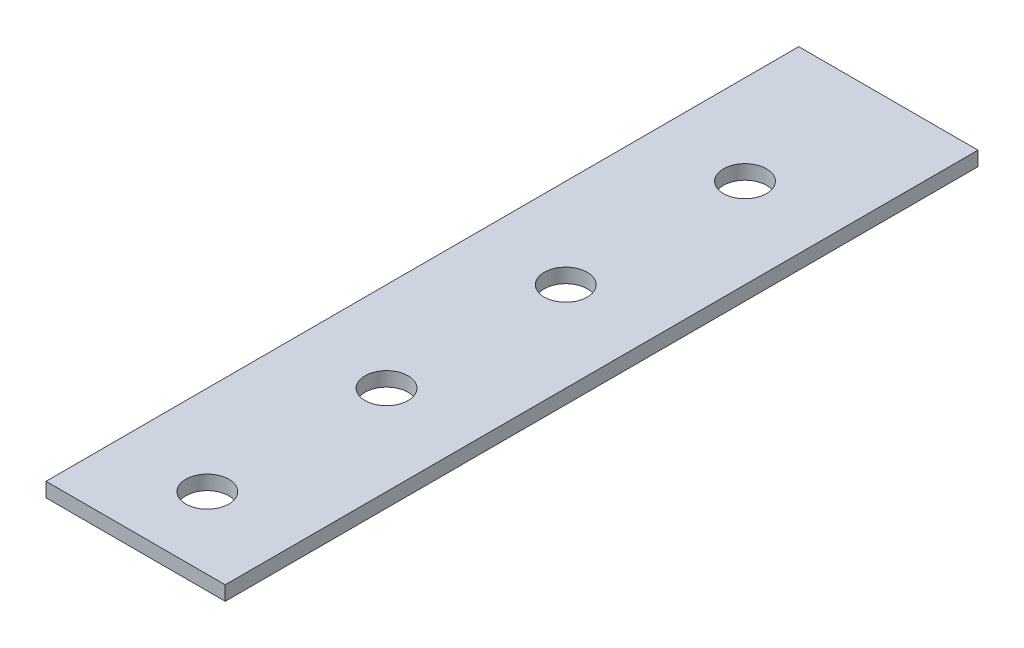
SolidWorks part; units mm, degrees
ref_plane "Front Plane" through (0, 0, 0) normal (0, 0, 1) x (1, 0, 0)
ref_plane "Top Plane" through (0, 0, 0) normal (0, 1, 0) x (1, 0, 0)
ref_plane "Right Plane" through (0, 0, 0) normal (1, 0, 0) x (0, 0, -1)
sketch "Sketch1" plane through (0, 0, 0) normal (0, 1, 0) x (1, 0, 0)
  line L1 (-12.5, -52.5) -> (12.5, -52.5)
  line L2 (-12.5, -52.5) -> (-12.5, 52.5)
  line L3 (-12.5, 52.5) -> (12.5, 52.5)
  line L4 (12.5, -52.5) -> (12.5, 52.5)
  line L5 (-12.5, -52.5) -> (12.5, 52.5) construction
  line L6 (-12.5, 52.5) -> (12.5, -52.5) construction
  point P0 (0, 0)
  dimension "D1" = 105
  dimension "D2" = 25
extrude "Boss-Extrude1" add sketch "Sketch1" along normal blind 2
sketch "Sketch2" plane through (0, 2, 0) normal (0, 1, 0) x (1, 0, 0)
  line L0 (-12.5, -52.5) -> (12.5, -52.5) construction
  line L1 (-12.5, 52.5) -> (-12.5, -52.5) construction
  circle A0 centre (0, -42.5) radius 3
  circle A1 centre (0, -17.5) radius 3
  circle A2 centre (0, 7.5) radius 3
  circle A3 centre (0, 32.5) radius 3
  dimension "D1" = 6
  dimension "D2" = 6
  dimension "D3" = 6
  dimension "D4" = 6
  dimension "D5" = 10
  dimension "D6" = 12.5
  dimension "D7" = 25
  dimension "D8" = 12.5
  dimension "D9" = 25
  dimension "D10" = 12.5
  dimension "D11" = 12.5
  dimension "D12" = 25
extrude "Cut-Extrude1" cut sketch "Sketch2" against normal through all
